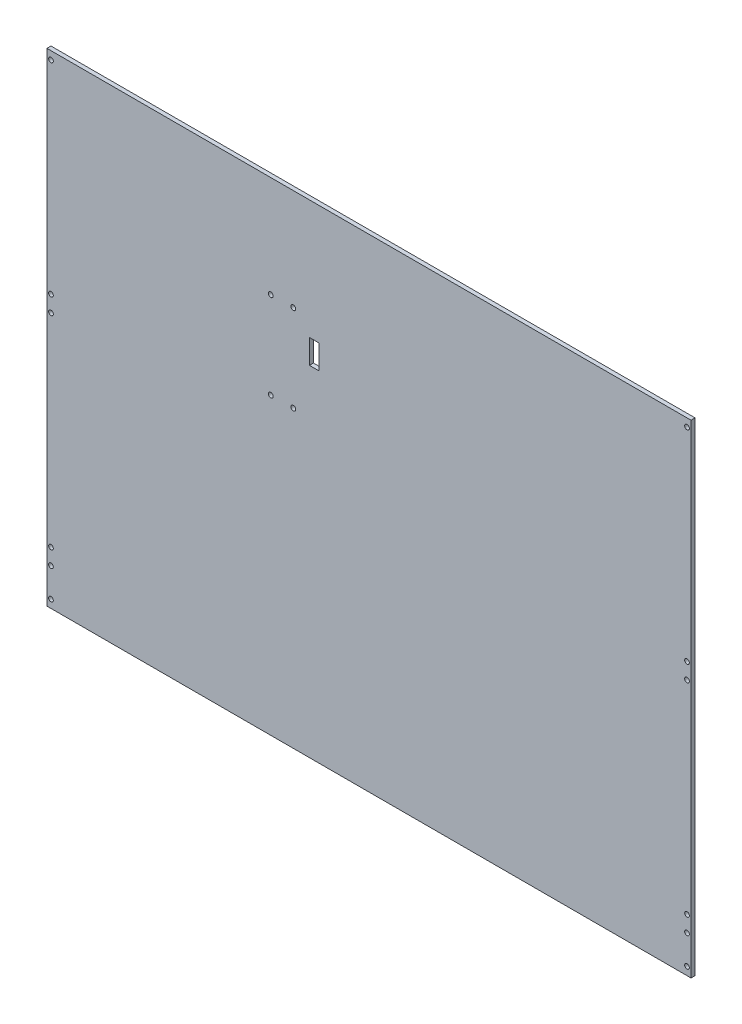
SolidWorks part; units mm, degrees
ref_plane "Front Plane" through (0, 0, 0) normal (0, 0, 1) x (1, 0, 0)
ref_plane "Top Plane" through (0, 0, 0) normal (0, 1, 0) x (1, 0, 0)
ref_plane "Right Plane" through (0, 0, 0) normal (1, 0, 0) x (0, 0, -1)
sketch "Sketch1" plane through (0, 0, 0) normal (0, 0, 1) x (1, 0, 0)
  line L1 (-254, -190.5) -> (254, -190.5)
  line L2 (-254, -190.5) -> (-254, 190.5)
  line L3 (-254, 190.5) -> (254, 190.5)
  line L4 (254, -190.5) -> (254, 190.5)
  line L5 (-254, -190.5) -> (254, 190.5) construction
  line L6 (-254, 190.5) -> (254, -190.5) construction
  point P0 (0, 0)
  dimension "D1" = 508
  dimension "D2" = 381
extrude "Boss-Extrude1" add sketch "Sketch1" along normal blind 3.175
sketch "Sketch3" plane through (0, 0, 3.175) normal (0, 0, 1) x (1, 0, 0)
  line L0 (-254, 190.5) -> (-254, -190.5) construction
  line L1 (-46.99, 77.47) -> (-39.37, 77.47)
  line L2 (-46.99, 77.47) -> (-46.99, 96.52)
  line L3 (-46.99, 96.52) -> (-39.37, 96.52)
  line L4 (-39.37, 77.47) -> (-39.37, 96.52)
  line L5 (254, 190.5) -> (-254, 190.5) construction
  dimension "D1" = 207.01
  dimension "D2" = 7.62
  dimension "D3" = 113.03
  dimension "D4" = 19.05
extrude "Cut-Extrude2" cut sketch "Sketch3" against normal up to surface (3.175 mm away) up to face at (0, 0, 0)
sketch "Sketch2" plane through (0, 0, 3.175) normal (0, 0, 1) x (1, 0, 0)
  line L0 (-250.825, 190.5) -> (-250.825, -190.5) construction
  line L1 (254, 190.5) -> (-254, 190.5) construction
  line L2 (-254, -190.5) -> (254, -190.5) construction
  line L3 (250.825, 190.5) -> (250.825, -190.5) construction
  line L4 (254, -190.5) -> (254, 190.5) construction
  line L5 (-254, 190.5) -> (-254, -190.5) construction
  line L6 (0, 0) -> (0, -50000) construction
  line L8 (-39.37, 96.52) -> (-46.99, 96.52) construction
  circle A0 centre (-250.825, -184.15) radius 1.8542
  circle A1 centre (-250.825, 184.15) radius 1.8542
  circle A2 centre (250.825, 184.15) radius 1.8542
  circle A3 centre (250.825, -184.15) radius 1.8542
  circle A4 centre (-250.825, 24.13) radius 1.8542
  circle A5 centre (250.825, 24.13) radius 1.8542
  circle A6 centre (-250.825, 11.43) radius 1.8542
  circle A7 centre (-250.825, -148.59) radius 1.8542
  circle A8 centre (-250.825, -161.29) radius 1.8542
  circle A9 centre (250.825, -161.29) radius 1.8542
  circle A10 centre (250.825, -148.59) radius 1.8542
  circle A11 centre (250.825, 11.43) radius 1.8542
  circle A12 centre (-77.4887, 110.49) radius 1.905
  circle A13 centre (-77.4887, 41.91) radius 1.905
  circle A14 centre (-59.7087, 110.49) radius 1.905
  circle A15 centre (-59.7087, 41.91) radius 1.905
  point P33 (0, -190.5)
  point P40 (0, 0)
  point P41 (0, 0)
  point P42 (0, 0)
  point P43 (-82.996, 60.156)
  point P44 (0, 0)
  point P54 (0, 0)
  point P57 (0, 0)
  dimension "D3" = 3.7084
  dimension "D10" = 12.7
  dimension "D14" = 3.81
  dimension "D12" = 17.78
  dimension "D1" = 3.175
  dimension "D2" = 3.175
  dimension "D4" = 6.35
  dimension "D5" = 6.35
  dimension "D6" = 6.35
  dimension "D7" = 6.35
  dimension "D8" = 160.02
  dimension "D9" = 160.02
  dimension "D11" = 29.21
  dimension "D13" = 68.58
  dimension "D15" = 12.7187
  dimension "D16" = 13.97
extrude "Cut-Extrude1" cut sketch "Sketch2" against normal blind 3.175
